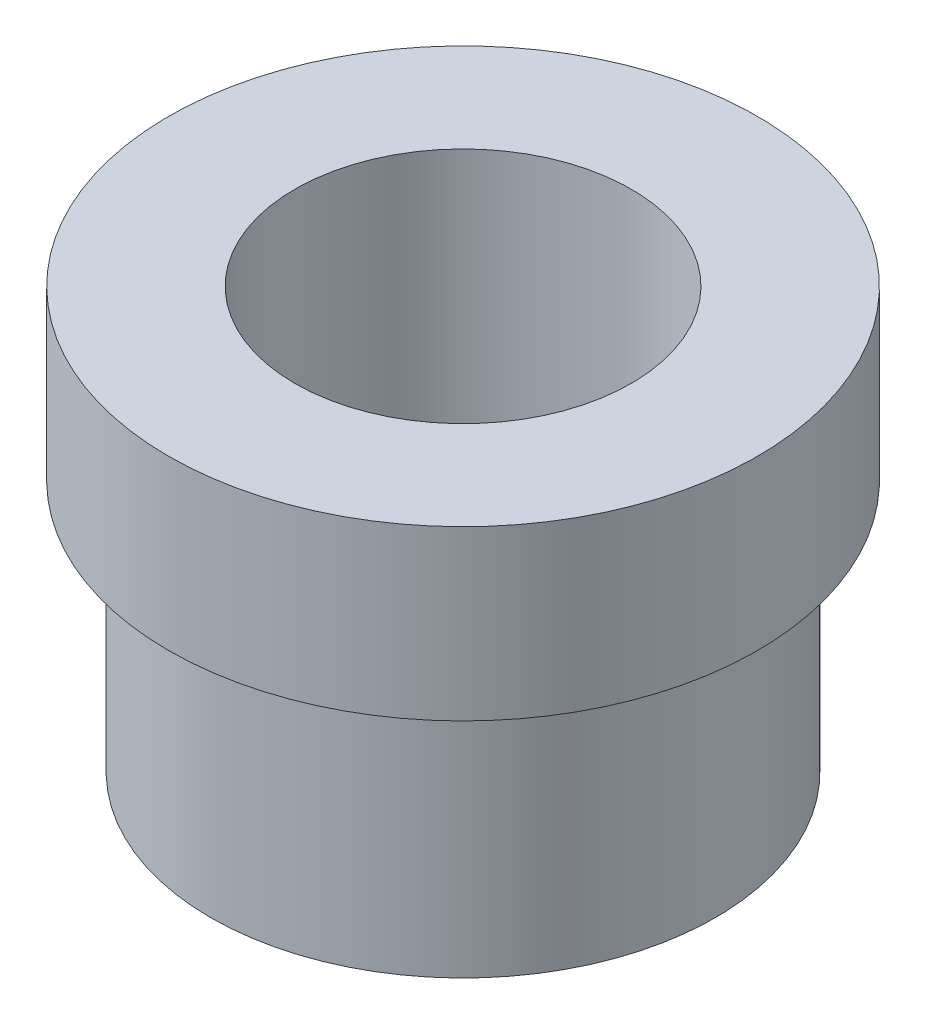
SolidWorks part; units mm, degrees
material "Plain Carbon Steel"
ref_plane "Front Plane" through (0, 0, 0) normal (0, 0, 1) x (1, 0, 0)
ref_plane "Top Plane" through (0, 0, 0) normal (0, 1, 0) x (1, 0, 0)
ref_plane "Right Plane" through (0, 0, 0) normal (1, 0, 0) x (0, 0, -1)
sketch "Sketch1" plane through (0, 0, 0) normal (0, 0, 1) x (1, 0, 0)
  line L0 (0, 61.8349) -> (0, -68.8073) construction
  line L1 (10, 0) -> (10, 25)
  line L2 (17.5, 25) -> (17.5, 15)
  line L3 (17.5, 15) -> (15, 15)
  line L4 (15, 15) -> (15, 0)
  line L5 (15, 0) -> (10, 0)
  line L6 (10, 25) -> (17.5, 25)
  point P5 (0, 0)
  dimension "D1" = 20
  dimension "D2" = 30
  dimension "D3" = 25
  dimension "D4" = 10
  dimension "D5" = 35
revolve "Revolve1" add sketch "Sketch1" angle 360 about L0
